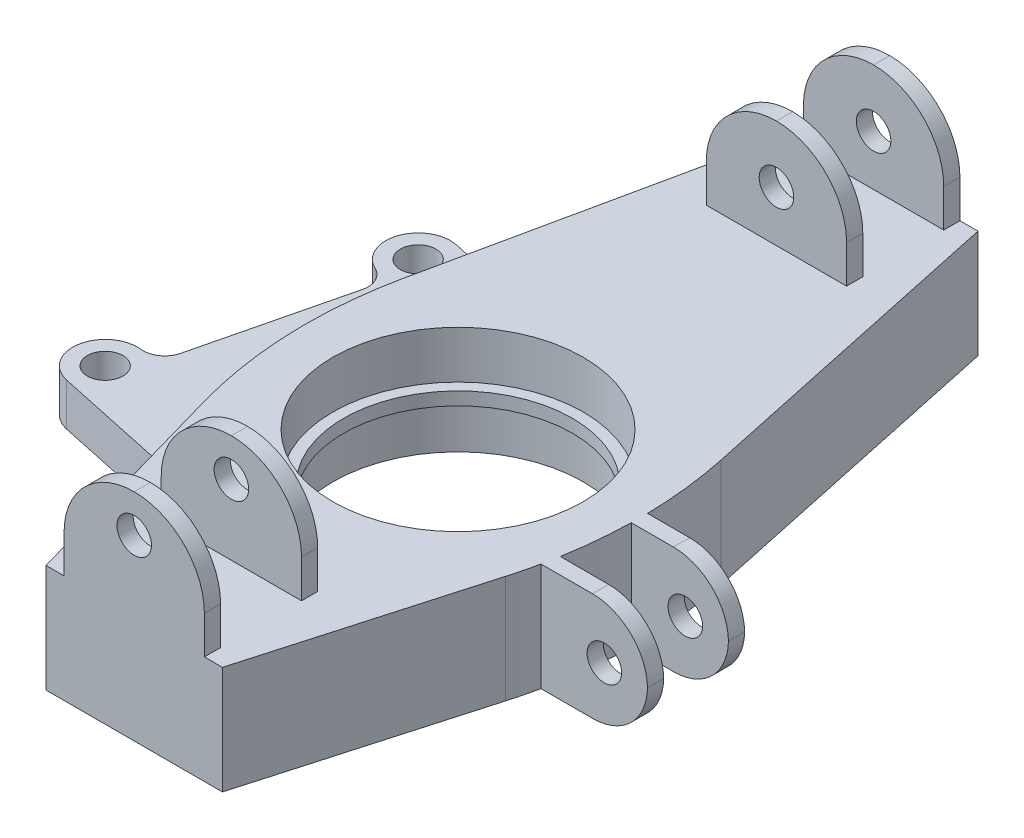
SolidWorks part; units mm, degrees
ref_plane "Front Plane" through (0, 0, 0) normal (0, 0, 1) x (1, 0, 0)
ref_plane "Top Plane" through (0, 0, 0) normal (0, 1, 0) x (1, 0, 0)
ref_plane "Right Plane" through (0, 0, 0) normal (1, 0, 0) x (0, 0, -1)
sketch "Sketch1" plane through (0, 0, 0) normal (0, 1, 0) x (1, 0, 0)
  line L1 (37.1752, 24.7132) -> (20.7644, 101.6)
  line L2 (20.7644, 101.6) -> (-20.7644, 101.6)
  line L4 (20.7644, 101.6) -> (20.7644, -76.2) construction
  line L8 (0, 0) -> (0, 101.6) construction
  line L9 (0, 0) -> (42.4501, 0) construction
  line L10 (35.5332, -24.3048) -> (20.7644, -76.2)
  line L11 (20.7644, -76.2) -> (-20.7644, -76.2)
  line L12 (-37.1752, 24.7132) -> (-20.7644, 101.6)
  line L13 (-35.5332, -24.3048) -> (-20.7644, -76.2)
  line L14 (-20.7644, 101.6) -> (-20.7644, -76.2) construction
  circle A0 centre (0, 0) radius 29.464
  circle A2 centre (0, 0) radius 120.65
  arc A4 (-37.1752, 24.7132) -> (-35.5332, -24.3048) centre (62.1866, 3.5052) ccw
  arc A5 (35.5332, -24.3048) -> (37.1752, 24.7132) centre (-62.1866, 3.5052) ccw
  point P9 (0, -76.2)
  point P10 (0, -29.464)
  point P11 (29.464, 0)
  point P16 (-29.464, 0)
  point P18 (-42.4501, 0)
  dimension "D2" = 58.928
  dimension "D3" = 12.7
  dimension "D4" = 101.6
  dimension "D5" = 177.8
  dimension "D1" = 241.3
  dimension "D6" = 101.6
extrude "Base" add sketch "Sketch1" along normal blind 25.4 contours L12 L13 L11 L10 L1 L2 A0 region at (37.4126, 0, -0.1687)
sketch "Sketch2" plane through (0, 0, 0) normal (0, 1, 0) x (1, 0, 0)
  line L0 (16.51, 101.6) -> (16.51, 97.79)
  line L1 (0, 101.6) -> (0, -76.2) construction
  line L2 (16.51, 97.79) -> (-16.51, 97.79)
  line L3 (-16.51, 97.79) -> (-16.51, 101.6)
  line L4 (20.7644, 101.6) -> (-20.7644, 101.6) construction
  line L5 (-16.51, 101.6) -> (16.51, 101.6)
  line L11 (20.7644, 101.6) -> (-20.7644, 101.6) construction
  line L12 (0, 0) -> (35.6331, 0) construction
  line L13 (-16.51, 78.74) -> (-16.51, 74.93)
  line L14 (-16.51, 74.93) -> (16.51, 74.93)
  line L15 (16.51, 74.93) -> (16.51, 78.74)
  line L16 (16.51, 78.74) -> (-16.51, 78.74)
  line L26 (16.51, -72.39) -> (-16.51, -72.39)
  line L32 (20.7644, -76.2) -> (-20.7644, -76.2) construction
  line L33 (-16.51, -72.39) -> (-16.51, -76.2)
  line L34 (-16.51, -76.2) -> (16.51, -76.2)
  line L35 (16.51, -76.2) -> (16.51, -72.39)
  line L36 (-16.51, -49.53) -> (16.51, -49.53)
  line L37 (16.51, -49.53) -> (16.51, -53.34)
  line L38 (16.51, -53.34) -> (-16.51, -53.34)
  line L39 (-16.51, -53.34) -> (-16.51, -49.53)
  point P4 (0, 101.6)
  point P45 (-16.51, 99.695)
  dimension "D2" = 3.81
  dimension "D3" = 3.81
  dimension "D4" = 19.05
  dimension "D5" = 2
  dimension "D11" = 33.02
extrude "A-Arms" add sketch "Sketch2" against normal blind 25.4
fillet "Fillet a-arm tab f" radius 16.51 8 edges at (16.51, -25.4, -99.695) (-16.51, -25.4, -76.835) (-16.51, -25.4, -99.695) (-16.51, -25.4, 74.295) (16.51, -25.4, 74.295) (-16.51, -25.4, 51.435) (16.51, -25.4, 51.435) (16.51, -25.4, -76.835)
ref_plane "Plane1" through (0, 1, 0) normal (0, -1, 0) x (-1, 0, 0)
sketch "Sketch3" plane through (0, 25.4, 0) normal (0, -1, 0) x (-1, 0, 0)
  line L0 (32.133, 48.3368) -> (53.1736, 52.8277)
  line L2 (34.3293, -28.5351) -> (71.4838, -20.6048)
  line L3 (55.1887, 32.6617) -> (63.5548, -1.731)
  line L5 (37.1752, 24.7132) -> (20.7644, 101.6) construction
  line L8 (35.5332, -24.3048) -> (20.7644, -76.2) construction
  line L9 (35.5332, -24.3048) -> (20.7644, -76.2) construction
  line L10 (37.1752, 24.7132) -> (20.7644, 101.6) construction
  line L11 (35.5332, -24.3048) -> (20.7644, -76.2)
  line L12 (37.1752, 24.7132) -> (20.7644, 101.6)
  circle A0 centre (0, 0) radius 71.12
  circle A1 centre (54.7642, 45.3756) radius 4.191
  circle A2 centre (69.8932, -13.1527) radius 4.191
  arc A3 (57.9805, 38.4677) -> (53.1736, 52.8277) centre (54.7642, 45.3756) ccw
  arc A4 (71.4838, -20.6048) -> (69.0518, -5.5793) centre (69.8932, -13.1527) ccw
  arc A5 (63.5548, -1.731) -> (69.0518, -5.5793) centre (68.4909, -0.5303) ccw
  arc A6 (55.1887, 32.6617) -> (57.9805, 38.4677) centre (60.1248, 33.8624) cw
  arc A7 (35.5332, -24.3048) -> (37.1752, 24.7132) centre (-62.1866, 3.5052) ccw construction
  arc A8 (35.5332, -24.3048) -> (37.1752, 24.7132) centre (-62.1866, 3.5052) ccw
  dimension "D1" = 60.452
  dimension "D2" = 142.24
  dimension "D3" = 8.382
  dimension "D4" = 8.382
  dimension "D5" = 15.24
  dimension "D6" = 15.24
  dimension "D7" = 5.08
extrude "Boss-Extrude3" add sketch "Sketch3" along normal blind 10 contours A6 L3 A5 A4 A0 A2 L2 L0 A1 A3 | A3 A0 A1 L0 | A4 L2 A0 A2 region at (-49.0548, 25.4, -9.0509) region at (-50.9588, 25.4, -52.1564) region at (-68.6224, 25.4, 19.375)
sketch "Sketch6" plane through (0, 0, -101.6) normal (0, 0, -1) x (-1, 0, 0)
  line L0 (0, -25.4) -> (0, 3.0923) construction
  circle A1 centre (0, -11.8937) radius 4.064
  dimension "D1" = 14.986
  dimension "D2" = 8.128
extrude "Tab Holes 1" cut sketch "Sketch6" against normal blind 38.1
sketch "Sketch7" plane through (0, 0, 49.53) normal (0, 0, -1) x (-1, 0, 0)
  line L0 (0, -25.4) -> (0, 0) construction
  circle A0 centre (0, -16.51) radius 4.064
  dimension "D1" = 16.51
  dimension "D2" = 8.128
extrude "Tab Holes 2" cut sketch "Sketch7" against normal through all
ref_plane "midplane" through (0, 12.7, 0) normal (0, 1, 0) x (1, 0, 0)
sketch "Sketch8" plane through (0, 12.7, 0) normal (0, 1, 0) x (1, 0, 0)
  circle A2 centre (0, 0) radius 29.464 construction
  circle A3 centre (0, 0) radius 29.464
  circle A5 centre (0, 0) radius 26.924
  dimension "D1" = 2.54
extrude "mid-feature bearing" add sketch "Sketch8" along normal blind 1.524 and the other way blind 1.524
sketch "pushrod" plane through (0, 0, 0) normal (0, 1, 0) x (1, 0, 0)
  line L1 (-32.844, -79.7284) -> (0.176, -79.7284)
  line L2 (-32.844, -79.7284) -> (-32.844, -75.9184)
  line L3 (-32.844, -75.9184) -> (0.176, -75.9184)
  line L4 (0.176, -79.7284) -> (0.176, -75.9184)
  line L5 (-45.2966, -56.8684) -> (3.0871, -56.8684) construction
  line L6 (0.176, -75.9184) -> (-3.634, -75.9184)
  line L7 (0.176, -75.9184) -> (0.176, -56.8684)
  line L8 (0.176, -56.8684) -> (-3.634, -56.8684)
  line L9 (-3.634, -75.9184) -> (-3.634, -56.8684)
  line L10 (-32.844, -75.9184) -> (-29.034, -75.9184)
  line L11 (-32.844, -75.9184) -> (-32.844, -56.8684)
  line L12 (-32.844, -56.8684) -> (-29.034, -56.8684)
  line L13 (-29.034, -75.9184) -> (-29.034, -56.8684)
  dimension "D1" = 3.81
  dimension "D2" = 3.81
  dimension "D3" = 3.81
  dimension "D4" = 25.4
mirror "Mirror2" [suppressed] of bodies 108
delete or keep bodies "Body-Delete/Keep 1" [suppressed] type delete bodies bodies 108
ref_plane "Plane2" through (0, 0, -88.265) normal (0, 0, -1) x (-1, 0, 0)
ref_axis "Axis1" through (0, -11.8937, -74.93) along (0, 0, -1)
ref_point "top wishbont att pt"
ref_axis "Axis3" through (0, -16.51, 53.34) along (0, 0, -1)
ref_plane "Plane3" through (0, 0, 62.865) normal (0, 0, -1) x (-1, 0, 0)
ref_point "bottom wishbone"
sketch "Sketch10" plane through (0, 0, 0) normal (0, -1, 0) x (1, 0, 0)
  line L1 (37.9191, 13.856) -> (37.1831, 17.666)
  line L2 (39.3912, -1.384) -> (62.2593, -1.384)
  line L3 (62.2593, -1.384) -> (62.2593, -5.194)
  line L4 (62.2593, -5.194) -> (39.3993, -5.194)
  line L5 (62.2593, 13.856) -> (62.2593, 17.666)
  line L6 (62.2593, 17.666) -> (37.1831, 17.666)
  line L8 (37.9191, 13.856) -> (62.2593, 13.856)
  line L9 (35.5332, 24.3048) -> (20.7644, 76.2) construction
  line L10 (35.5332, 24.3048) -> (20.7644, 76.2)
  arc A1 (37.1752, -24.7132) -> (35.5332, 24.3048) centre (-62.1866, -3.5052) ccw construction
  arc A2 (37.1752, -24.7132) -> (35.5332, 24.3048) centre (-62.1866, -3.5052) ccw
  arc A3 (37.1752, -24.7132) -> (35.5332, 24.3048) centre (-62.1866, -3.5052) ccw construction
  arc M33 (37.1752, -24.7132) -> (35.5332, 24.3048) centre (-62.1866, -3.5052) ccw
  dimension "D1" = 19.05
  dimension "D2" = 22.86
  dimension "D3" = 3.81
  dimension "D4" = 3.81
extrude "Boss-Extrude4" add sketch "Sketch10" against normal up to surface (25.4 mm away) contours L8 L5 L6 M33 | L4 L3 L2 M33 region at (49.9106, 0, 15.7704) region at (50.8333, 0, -3.2889) up to face at (-26.6415, 25.4, -12.1227)
fillet "Fillet1" radius 12.954 4 edges at (62.2593, 25.4, 15.761) (62.2593, 25.4, -3.289) (62.2593, 0, 15.761) (62.2593, 0, -3.289)
sketch "Sketch11" plane through (0, 0, -5.194) normal (0, 0, -1) x (-1, 0, 0)
  line L0 (-62.2568, 12.7) -> (-48.6985, 12.7) construction
  circle A0 centre (-52.0968, 12.7) radius 4.064
  dimension "D1" = 10.16
extrude "Cut-Extrude1" cut sketch "Sketch11" against normal through all
ref_axis "rotation axis" through (0, -16.51, 62.865) along (0, 0.0305, -0.9995)
ref_axis "Axis5" through (52.0968, 12.7, -1.384) along (0, 0, -1)
ref_plane "Plane4" through (0, 0, 6.236) normal (0, 0, -1) x (-1, 0, 0)
ref_point "tierod"
mirror "Mirror5" about plane through (0, 0, 0) normal (0, 1, 0) of bodies 120
delete or keep bodies "Body-Delete/Keep 3" type delete bodies bodies 120
ref_axis "Axis6" through (0, 11.8937, -97.79) along (0, 0, -1)
ref_point "top wish 2"
ref_axis "Axis7" through (0, 16.51, 53.34) along (0, 0, -1)
ref_point "bottom wish 2"
ref_axis "rot ax" through (0, 16.51, 62.865) along (0, -0.0305, -0.9995)
ref_axis "Axis9" through (52.0968, -12.7, -1.384) along (0, 0, -1)
ref_point "tie in 2"
mirror "Mirror3" [suppressed] of bodies 111
mirror "Mirror4" [suppressed] of bodies 111
delete or keep bodies "Body-Delete/Keep 2" [suppressed] type delete bodies bodies 111
